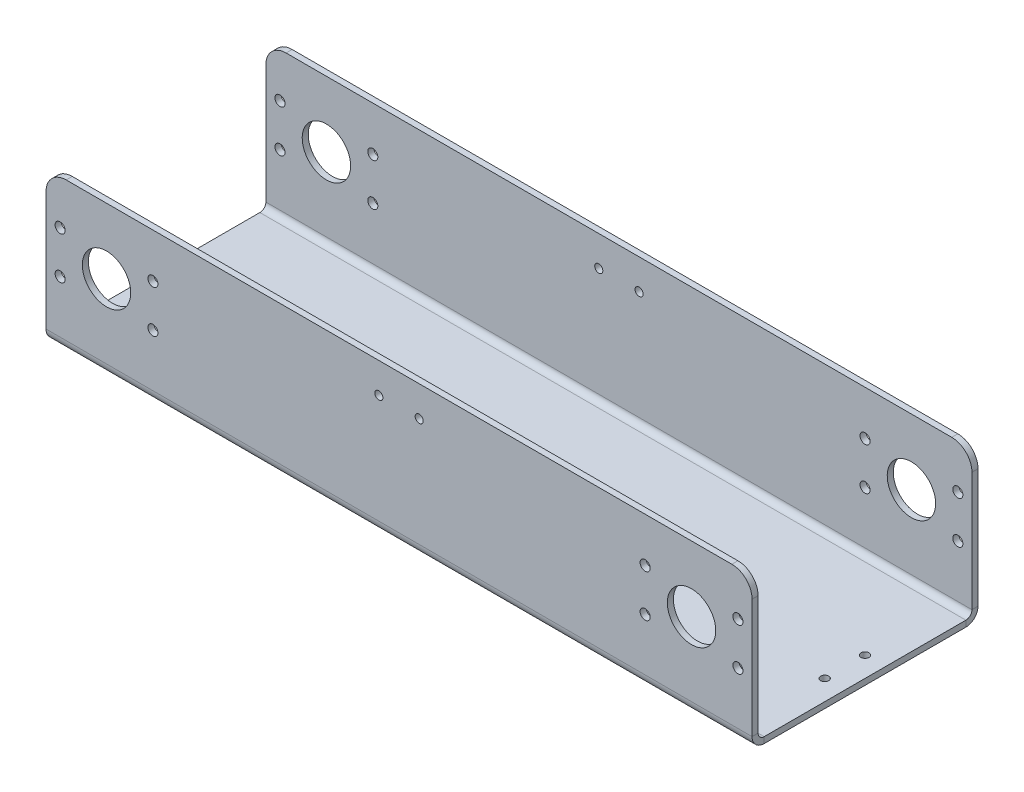
SolidWorks part; units mm, degrees
note: The reader was unsure of these and kept them because the rebuilt part matched: flange length of "邊線-凸緣1".
ref_plane "Front Plane" through (0, 0, 0) normal (0, 0, 1) x (1, 0, 0)
ref_plane "Top Plane" through (0, 0, 0) normal (0, 1, 0) x (1, 0, 0)
ref_plane "Right Plane" through (0, 0, 0) normal (1, 0, 0) x (0, 0, -1)
sketch "Sketch1" plane through (0, 0, 0) normal (0, 1, 0) x (1, 0, 0)
  line L0 (0, -50) -> (0, 50)
  line L1 (0, 50) -> (-350, 50)
  line L2 (-350, 50) -> (-350, -50)
  line L3 (-350, -50) -> (0, -50)
  point P4 (0, 0)
  dimension "D1" = 100
  dimension "D2" = 350
base flange "Base-Flange1" sketch "Sketch1" thickness 3 reverse thickness direction no parameters "D1"=3
edge flange "邊線-凸緣1" sketch "Sketch10" flange profiles "Sketch10", "Sketch11" flange angle 90 flange length 75 flange position bend outside bend radius 3 thickness 3 relief rectangular parameters "D6"=10, "D8"=1
sketch "Sketch10" plane through (0, 0, 50) normal (0, 0, 1) x (1, 0, 0)
  line L0 (-350, 0) -> (0, 0) construction
  line L1 (-350, 0) -> (0, 0)
  line L2 (-350, 0) -> (-350, 72)
  line L3 (-350, 72) -> (0, 72)
  line L4 (0, 72) -> (0, 0)
sketch "Sketch11" plane through (0, 0, -50) normal (0, 0, -1) x (-1, 0, 0)
  line L0 (0, 0) -> (350, 0) construction
  line L1 (0, 0) -> (350, 0)
  line L2 (0, 0) -> (0, 72)
  line L3 (0, 72) -> (350, 72)
  line L4 (350, 72) -> (350, 0)
bend "邊線彎折1" bend radius 3 bend angle 90 parameters "D5"=1
bend "邊線彎折2" bend radius 3 bend angle 90 parameters "D5"=2
hole_wizard "Ø5.0 (5) Diameter Hole1" positions "Sketch12" profile "Sketch13" hole size "Ø5.0" standard "ISO" end condition through all
sketch "Sketch12" plane through (0, 0, 56) normal (0, 0, 1) x (1, 0, 0)
  point P0 (-343, 50)
  point P3 (-343, 29)
  point P6 (-297, 50)
  point P9 (-297, 29)
sketch "Sketch13" plane through (-343, 50, 56) normal (1, 0, 0) x (0, -1, 0)
  line L0 (0, 0) -> (0, 112)
  line L1 (0, 112) -> (2.5, 112)
  line L2 (2.5, 112) -> (2.5, 0)
  line L5 (2.5, 0) -> (0, 0)
  line L11 (0, -6.35) -> (0, 107.95) construction
  dimension "Thru Hole Dia." = 5
  dimension "Thru Hole Depth" = 112
sketch "Sketch14" plane through (0, 0, 56) normal (0, 0, 1) x (1, 0, 0)
  circle A0 centre (-320, 39.5) radius 12
  dimension "D1" = 24
extrude "Cut-Extrude1" cut sketch "Sketch14" against normal through all both and the other way through all normal cut yes
ref_plane "Plane1" through (-175, 0, 0) normal (1, 0, 0) x (0, 0, -1)
mirror "Mirror1" about plane through (-175, 0, 0) normal (1, 0, 0) of "Ø5.0 (5) Diameter Hole1", "Cut-Extrude1"
sketch "Sketch15" plane through (0, 0, -53) normal (0, 0, 1) x (1, 0, 0)
  line L0 (-175, 72) -> (-175, 0) construction
  line L1 (-350, 72) -> (0, 72) construction
  line L2 (-175, -1.65) -> (-175, 1.65) construction
  line L3 (-185, 57) -> (-165, 57) construction
  point P9 (-175, 57)
  dimension "D1" = 20
  dimension "D2" = 15
hole_wizard "Ø4.0 (4) Diameter Hole1" positions "Sketch16" profile "Sketch17" hole size "Ø4.0" standard "ISO" end condition through all
sketch "Sketch16" plane through (0, 0, -53) normal (0, 0, 1) x (1, 0, 0)
  point P0 (-185, 57)
  point P3 (-165, 57)
sketch "Sketch17" plane through (-185, 57, -53) normal (1, 0, 0) x (0, -1, 0)
  line L0 (0, 0) -> (0, 3)
  line L1 (0, 3) -> (2, 3)
  line L2 (2, 3) -> (2, 0)
  line L5 (2, 0) -> (0, 0)
  line L11 (0, -6.35) -> (0, 107.95) construction
  dimension "Thru Hole Dia." = 4
  dimension "Thru Hole Depth" = 3
sketch "Sketch18" plane through (0, 0, 0) normal (0, 1, 0) x (1, 0, 0)
  line L0 (-350, 0) -> (0, 0) construction
  line L1 (-350, 50) -> (-350, -50) construction
  line L2 (-340, -10) -> (-340, 10) construction
  point P8 (-340, 0)
  dimension "D1" = 20
  dimension "D2" = 10
hole_wizard "Ø4.0 (4) Diameter Hole2" positions "Sketch19" profile "Sketch20" hole size "Ø4.0" standard "ISO" end condition through all
sketch "Sketch19" plane through (0, 0, 0) normal (0, 1, 0) x (1, 0, 0)
  point P0 (-340, 10)
  point P3 (-340, -10)
sketch "Sketch20" plane through (-340, 0, -10) normal (1, 0, 0) x (0, 0, 1)
  line L0 (0, 0) -> (0, 3)
  line L1 (0, 3) -> (2, 3)
  line L2 (2, 3) -> (2, 0)
  line L5 (2, 0) -> (0, 0)
  line L11 (0, -6.35) -> (0, 107.95) construction
  dimension "Thru Hole Dia." = 4
  dimension "Thru Hole Depth" = 3
mirror "Mirror2" about plane through (-175, 0, 0) normal (1, 0, 0) of "Ø4.0 (4) Diameter Hole2"
mirror "Mirror3" about plane through (0, 0, 0) normal (0, 0, 1) of "Ø4.0 (4) Diameter Hole1"
fillet "Fillet1" radius 10 4 edges at (-350, 72, 54.5) (-350, 72, -54.5) (0, 72, -54.5) (0, 72, 54.5)
sketch "彎折-線1" [suppressed] plane through (0, 0, 0) normal (0, 1, 0) x (1, 0, 0)
sketch "邊界方塊1" [suppressed] plane through (0, 0, 0) normal (0, 1, 0) x (1, 0, 0)
sheet metal parameters "鈑金1" thickness 3 parameters "D1"=3
flat pattern "平板-型式1" [suppressed]
sketch "彎折-線2" plane through (0, 0, 0) normal (0, 1, 0) x (1, 0, 0)
sketch3d "邊界方塊2" [suppressed]
  line L0 (0, -60, 0) -> (350, -60, 0) construction
  line L1 (0, 60, 0) -> (350, 60, 0) construction
  line L2 (0, -60, 0) -> (0, 60, 0) construction
  line L3 (350, -60, 0) -> (350, 60, 0) construction
sheet metal parameters "鈑金2" thickness 3 parameters "D1"=3
flat pattern "平板-型式1"
sketch "彎折-線2" plane through (0, 0, 0) normal (0, 1, 0) x (1, 0, 0)
  line L0 (0, 63.3387) -> (-350, 63.3387) construction
  line L1 (-350, -63.3387) -> (0, -63.3387) construction
  line L2 (0, 63.3387) -> (-350, 63.3387) construction
  line L3 (-350, -63.3387) -> (0, -63.3387) construction
sketch3d "邊界方塊2" [suppressed]
  line L0 (0, -135.6775, 0) -> (-350, -135.6775, 0) construction
  line L1 (0, 135.6775, 0) -> (-350, 135.6775, 0) construction
  line L2 (0, -135.6775, 0) -> (0, 135.6775, 0) construction
  line L3 (-350, -135.6775, 0) -> (-350, 135.6775, 0) construction
bend of the flat pattern "平板-<邊線彎折1>1"
bend of the flat pattern "平板-<邊線彎折2>1"
sheet metal parameters "鈑金3" thickness 3 parameters "D1"=3
flat pattern "平板-型式1"
sketch "彎折-線2" plane through (0, 0, 0) normal (0, 1, 0) x (1, 0, 0)
  line L0 (0, 63.3387) -> (-350, 63.3387) construction
  line L1 (-350, -63.3387) -> (0, -63.3387) construction
  line L2 (0, 63.3387) -> (-350, 63.3387) construction
  line L3 (-350, -63.3387) -> (0, -63.3387) construction
sketch3d "邊界方塊2" [suppressed]
  line L0 (0, -135.6775, 0) -> (-350, -135.6775, 0) construction
  line L1 (0, 135.6775, 0) -> (-350, 135.6775, 0) construction
  line L2 (0, -135.6775, 0) -> (0, 135.6775, 0) construction
  line L3 (-350, -135.6775, 0) -> (-350, 135.6775, 0) construction
bend of the flat pattern "平板-<邊線彎折1>1"
bend of the flat pattern "平板-<邊線彎折2>1"
sheet metal parameters "鈑金4" thickness 3 parameters "D1"=3
flat pattern "平板-型式1"
sketch "彎折-線2" plane through (0, 0, 0) normal (0, 1, 0) x (1, 0, 0)
  line L0 (0, 53.3387) -> (-350, 53.3387) construction
  line L1 (-350, -53.3387) -> (0, -53.3387) construction
  line L2 (0, 53.3387) -> (-350, 53.3387) construction
  line L3 (-350, -53.3387) -> (0, -53.3387) construction
sketch3d "邊界方塊2" [suppressed]
  line L0 (0, -125.6775, 0) -> (-350, -125.6775, 0) construction
  line L1 (0, 125.6775, 0) -> (-350, 125.6775, 0) construction
  line L2 (0, -125.6775, 0) -> (0, 125.6775, 0) construction
  line L3 (-350, -125.6775, 0) -> (-350, 125.6775, 0) construction
bend of the flat pattern "平板-<邊線彎折1>1"
bend of the flat pattern "平板-<邊線彎折2>1"
sheet metal parameters "鈑金5" thickness 3 parameters "D1"=3
flat pattern "平板-型式1"
sketch "彎折-線2" plane through (0, 0, 0) normal (0, 1, 0) x (1, 0, 0)
  line L0 (0, 53.3387) -> (-350, 53.3387) construction
  line L1 (-350, -53.3387) -> (0, -53.3387) construction
  line L2 (0, 53.3387) -> (-350, 53.3387) construction
  line L3 (-350, -53.3387) -> (0, -53.3387) construction
sketch3d "邊界方塊2" [suppressed]
  line L0 (0, -125.6775, 0) -> (-350, -125.6775, 0) construction
  line L1 (0, 125.6775, 0) -> (-350, 125.6775, 0) construction
  line L2 (0, -125.6775, 0) -> (0, 125.6775, 0) construction
  line L3 (-350, -125.6775, 0) -> (-350, 125.6775, 0) construction
bend of the flat pattern "平板-<邊線彎折1>1"
bend of the flat pattern "平板-<邊線彎折2>1"
sheet metal parameters "鈑金6" thickness 3 parameters "D1"=3
flat pattern "平板-型式1" [suppressed]
sketch "彎折-線2" plane through (0, 0, 0) normal (0, 1, 0) x (1, 0, 0)
  line L0 (0, 53.3387) -> (-350, 53.3387) construction
  line L1 (-350, -53.3387) -> (0, -53.3387) construction
  line L2 (0, 53.3387) -> (-350, 53.3387) construction
  line L3 (-350, -53.3387) -> (0, -53.3387) construction
sketch3d "邊界方塊2" [suppressed]
  line L0 (0, -125.6775, 0) -> (-350, -125.6775, 0) construction
  line L1 (0, 125.6775, 0) -> (-350, 125.6775, 0) construction
  line L2 (0, -125.6775, 0) -> (0, 125.6775, 0) construction
  line L3 (-350, -125.6775, 0) -> (-350, 125.6775, 0) construction
bend of the flat pattern "平板-<邊線彎折1>1"
bend of the flat pattern "平板-<邊線彎折2>1"
sketch "Sketch15-1" [suppressed] plane through (0, 0, -53.6775) normal (0, 1, 0) x (1, 0, 0)
  line L0 (-175, 72) -> (-175, 0) construction
  line L1 (-350, 72) -> (0, 72) construction
  line L3 (-185, 57) -> (-165, 57) construction
  point P9 (-175, 57)
  dimension "D1" = 20
  dimension "D2" = 15
sheet metal parameters "鈑金7" thickness 3 parameters "D1"=3
flat pattern "平板-型式1" [suppressed]
sketch "彎折-線2" plane through (0, 0, 0) normal (0, 1, 0) x (1, 0, 0)
  line L0 (0, 53.3387) -> (-350, 53.3387) construction
  line L1 (-350, -53.3387) -> (0, -53.3387) construction
  line L2 (0, 53.3387) -> (-350, 53.3387) construction
  line L3 (-350, -53.3387) -> (0, -53.3387) construction
sketch3d "邊界方塊2" [suppressed]
  line L0 (0, -125.6775, 0) -> (-350, -125.6775, 0) construction
  line L1 (0, 125.6775, 0) -> (-350, 125.6775, 0) construction
  line L2 (0, -125.6775, 0) -> (0, 125.6775, 0) construction
  line L3 (-350, -125.6775, 0) -> (-350, 125.6775, 0) construction
bend of the flat pattern "平板-<邊線彎折1>1"
bend of the flat pattern "平板-<邊線彎折2>1"
sketch "Sketch15-1" [suppressed] plane through (0, 0, -53.6775) normal (0, 1, 0) x (1, 0, 0)
  line L0 (-175, 72) -> (-175, 0) construction
  line L1 (-350, 72) -> (0, 72) construction
  line L3 (-185, 57) -> (-165, 57) construction
  point P9 (-175, 57)
  dimension "D1" = 20
  dimension "D2" = 15
sheet metal parameters "鈑金8" thickness 3 parameters "D1"=3
flat pattern "平板-型式1" [suppressed]
sketch "彎折-線2" plane through (0, 0, 0) normal (0, 1, 0) x (1, 0, 0)
  line L0 (0, 53.3387) -> (-350, 53.3387) construction
  line L1 (-350, -53.3387) -> (0, -53.3387) construction
  line L2 (0, 53.3387) -> (-350, 53.3387) construction
  line L3 (-350, -53.3387) -> (0, -53.3387) construction
sketch3d "邊界方塊2" [suppressed]
  line L0 (0, -125.6775, 0) -> (-350, -125.6775, 0) construction
  line L1 (0, 125.6775, 0) -> (-350, 125.6775, 0) construction
  line L2 (0, -125.6775, 0) -> (0, 125.6775, 0) construction
  line L3 (-350, -125.6775, 0) -> (-350, 125.6775, 0) construction
bend of the flat pattern "平板-<邊線彎折1>1"
bend of the flat pattern "平板-<邊線彎折2>1"
sketch "Sketch15-1" [suppressed] plane through (0, 0, -53.6775) normal (0, 1, 0) x (1, 0, 0)
  line L0 (-175, 72) -> (-175, 0) construction
  line L1 (-350, 72) -> (0, 72) construction
  line L3 (-185, 57) -> (-165, 57) construction
  point P9 (-175, 57)
  dimension "D1" = 20
  dimension "D2" = 15
sheet metal parameters "鈑金9" thickness 3 parameters "D1"=3
flat pattern "平板-型式1" [suppressed]
sketch "彎折-線2" plane through (0, 0, 0) normal (0, 1, 0) x (1, 0, 0)
  line L0 (0, 53.3387) -> (-350, 53.3387) construction
  line L1 (-350, -53.3387) -> (0, -53.3387) construction
  line L2 (0, 53.3387) -> (-350, 53.3387) construction
  line L3 (-350, -53.3387) -> (0, -53.3387) construction
sketch3d "邊界方塊2" [suppressed]
  line L0 (-350, -125.6775, 0) -> (0, -125.6775, 0) construction
  line L1 (-350, 125.6775, 0) -> (0, 125.6775, 0) construction
  line L2 (-350, -125.6775, 0) -> (-350, 125.6775, 0) construction
  line L3 (0, -125.6775, 0) -> (0, 125.6775, 0) construction
bend of the flat pattern "平板-<邊線彎折1>1"
bend of the flat pattern "平板-<邊線彎折2>1"
sketch "Sketch15-1" [suppressed] plane through (0, 0, -53.6775) normal (0, 1, 0) x (1, 0, 0)
  line L0 (-175, 72) -> (-175, 0) construction
  line L1 (-340, 72) -> (-10, 72) construction
  line L3 (-185, 57) -> (-165, 57) construction
  point P9 (-175, 57)
  dimension "D1" = 20
  dimension "D2" = 15
